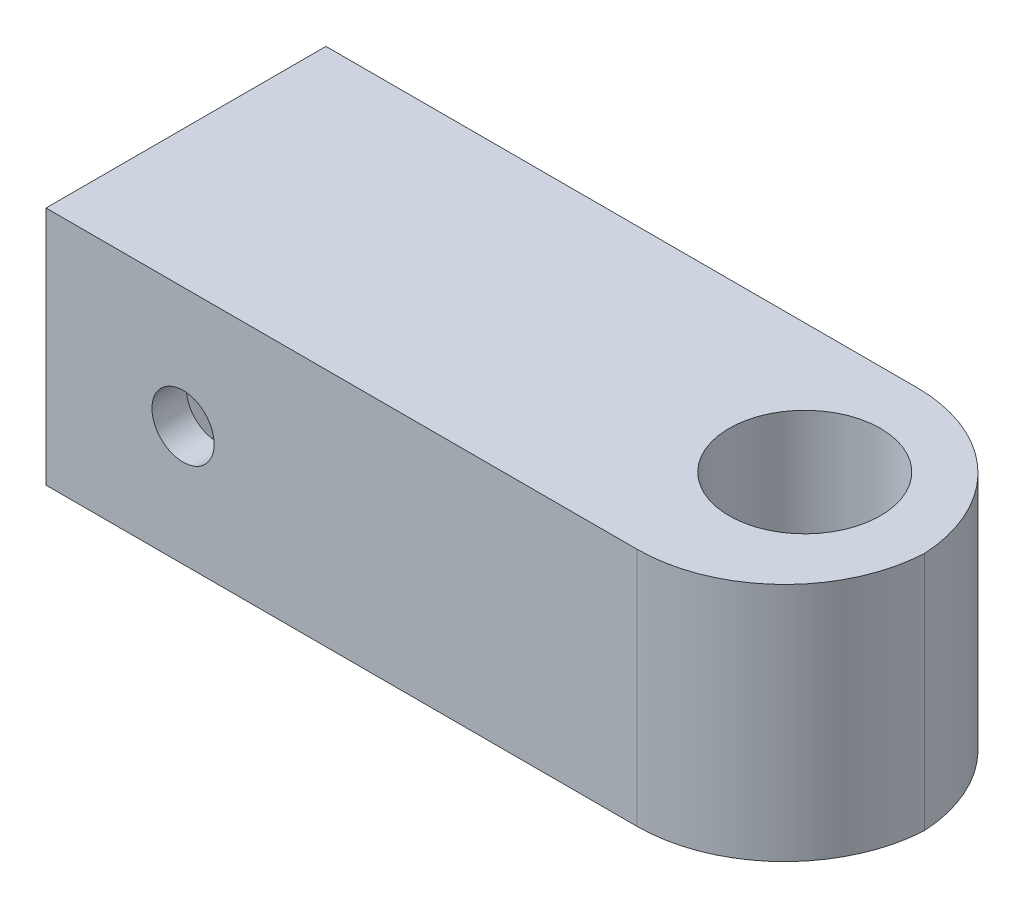
SolidWorks part; units mm, degrees
ref_plane "Plano frontal" through (0, 0, 0) normal (0, 0, 1) x (1, 0, 0)
ref_plane "Plano superior" through (0, 0, 0) normal (0, 1, 0) x (1, 0, 0)
ref_plane "Plano direito" through (0, 0, 0) normal (1, 0, 0) x (0, 0, -1)
sketch "Esboço2" plane through (0, 0, 0) normal (0, 1, 0) x (1, 0, 0)
  line L1 (-55, 0) -> (55, 0) construction
  line L3 (20, -5) -> (20, 7)
  line L4 (20, 7) -> (-20, 7)
  line L5 (-20, -5) -> (-20, 7)
  line L7 (-20, -5) -> (-20, -8.161)
  line L8 (-20, -8.161) -> (20, -8.161)
  line L9 (20, -5) -> (20, -8.161)
  circle A0 centre (12.9306, 0) radius 4.1
  dimension "D3" = 7
  dimension "D2" = 40
extrude "Ressalto-extrusão1" add sketch "Esboço2" along normal blind 13
sketch "Esboço3" plane through (-20, 0, 0) normal (-1, 0, 0) x (0, 0, 1)
  line L0 (0, -55) -> (0, 55) construction
  line L1 (3.5, 3) -> (-3.5, 3)
  line L2 (3.5, 3) -> (3.5, 10)
  line L3 (3.5, 10) -> (-3.5, 10)
  line L4 (-3.5, 3) -> (-3.5, 10)
  line L5 (3.5, 3) -> (-3.5, 10) construction
  line L6 (3.5, 10) -> (-3.5, 3) construction
  point P0 (0, 6.5)
extrude "Corte-extrusão1" cut sketch "Esboço3" against normal blind 26
sketch "Esboço7" plane through (0, 0, 3.5) normal (0, 0, -1) x (-1, 0, 0)
  line L1 (8.8825, 6.4759) -> (10.73, 3.2759)
  line L2 (10.73, 3.2759) -> (14.425, 3.2759)
  line L3 (14.425, 3.2759) -> (16.2725, 6.4759)
  line L4 (16.2725, 6.4759) -> (14.425, 9.6759)
  line L5 (14.425, 9.6759) -> (10.73, 9.6759)
  line L6 (10.73, 9.6759) -> (8.8825, 6.4759)
  circle A0 centre (12.5775, 6.4759) radius 3.2 construction
extrude "Corte-extrusão2" cut sketch "Esboço7" against normal blind 2.8
sketch "Esboço10" plane through (0, 0, 6.3) normal (0, 0, -1) x (-1, 0, 0)
  circle A0 centre (12.5775, 6.4759) radius 1.6837
extrude "Corte-extrusão3" cut sketch "Esboço10" against normal blind 2.8
fillet "Filete1" radius 8 2 edges at (20, 6.5, -7) (20, 6.5, 8.161)
